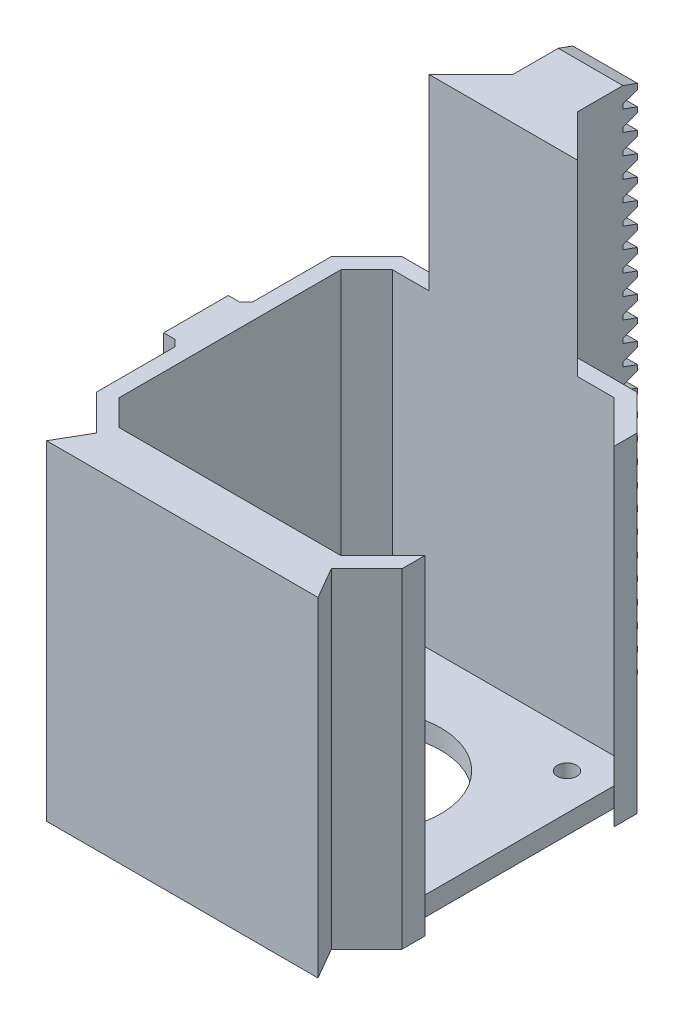
SolidWorks part; units mm, degrees
ref_plane "Front Plane" through (0, 0, 0) normal (0, 0, 1) x (1, 0, 0)
ref_plane "Top Plane" through (0, 0, 0) normal (0, 1, 0) x (1, 0, 0)
ref_plane "Right Plane" through (0, 0, 0) normal (1, 0, 0) x (0, 0, -1)
sketch "Sketch1" plane through (0, 0, 0) normal (0, 1, 0) x (1, 0, 0)
  line L0 (-21.15, 17.15) -> (-17.15, 21.15)
  line L1 (-17.15, -21.15) -> (17.15, -21.15)
  line L2 (-21.15, -17.15) -> (-21.15, 17.15)
  line L3 (-17.15, 21.15) -> (17.15, 21.15)
  line L4 (21.15, -17.15) -> (21.15, 17.15)
  line L5 (-21.15, -21.15) -> (21.15, 21.15) construction
  line L6 (-21.15, 21.15) -> (21.15, -21.15) construction
  line L7 (-21.15, -17.15) -> (-17.15, -21.15)
  line L8 (17.15, -21.15) -> (21.15, -17.15)
  line L9 (17.15, 21.15) -> (21.15, 17.15)
  circle A0 centre (-15.5, 15.5) radius 1.5
  circle A1 centre (15.5, 15.5) radius 1.5
  circle A2 centre (15.5, -15.5) radius 1.5
  circle A3 centre (-15.5, -15.5) radius 1.5
  circle A4 centre (0, 0) radius 11.5
  point P0 (0, 0)
  dimension "D3" = 3
  dimension "D4" = 3
  dimension "D9" = 3
  dimension "D10" = 3
  dimension "D12" = 23
  dimension "D1" = 42.3
  dimension "D2" = 42.3
  dimension "D11" = 31
extrude "Boss-Extrude1" add sketch "Sketch1" along normal blind 3
sketch "Sketch5" plane through (0, 0, 0) normal (0, 1, 0) x (1, 0, 0)
  line L0 (21.15, -17.15) -> (23.65, -14.65)
  line L1 (23.65, -14.65) -> (23.65, 14.65) construction
  line L16 (-23.65, 18.1855) -> (-23.65, -18.1855)
  line L17 (-23.65, -18.1855) -> (-18.1855, -23.65)
  line L18 (-18.1855, -23.65) -> (18.1855, -23.65)
  line L19 (18.1855, -23.65) -> (23.65, -18.1855)
  line L20 (23.65, -18.1855) -> (23.65, 18.1855)
  line L21 (23.65, 18.1855) -> (18.1855, 23.65)
  line L22 (18.1855, 23.65) -> (-18.1855, 23.65)
  line L23 (-18.1855, 23.65) -> (-23.65, 18.1855)
  line L24 (-23.65, 14.65) -> (-23.65, -18.1855)
  line L25 (-23.65, -18.1855) -> (-18.1855, -23.65)
  line L26 (-18.1855, -23.65) -> (18.1855, -23.65)
  line L27 (18.1855, -23.65) -> (23.65, -18.1855)
  line L28 (23.65, -18.1855) -> (23.65, -14.65)
  line L29 (23.65, 18.1855) -> (18.1855, 23.65)
  line L30 (18.1855, 23.65) -> (-18.1855, 23.65)
  line L31 (-18.1855, 23.65) -> (-23.65, 18.1855)
  line L32 (-21.15, 17.15) -> (-23.65, 14.65) construction
  line L33 (21.15, 17.15) -> (23.65, 14.65)
  line L34 (-23.65, 18.1855) -> (-23.65, 14.65)
  line L35 (23.65, 14.65) -> (23.65, 18.1855)
  line L40 (-21.15, 17.15) -> (-21.15, -17.15)
  line L41 (-21.15, -17.15) -> (-17.15, -21.15)
  line L42 (-17.15, -21.15) -> (17.15, -21.15)
  line L43 (17.15, -21.15) -> (21.15, -17.15)
  line L44 (21.15, -17.15) -> (21.15, 17.15)
  line L45 (21.15, 17.15) -> (17.15, 21.15)
  line L46 (17.15, 21.15) -> (-17.15, 21.15)
  line L47 (-17.15, 21.15) -> (-21.15, 17.15)
  line L48 (-21.15, 17.15) -> (-21.15, -17.15)
  line L49 (-21.15, -17.15) -> (-17.15, -21.15)
  line L50 (-17.15, -21.15) -> (17.15, -21.15)
  line L51 (17.15, -21.15) -> (21.15, -17.15)
  line L52 (21.15, -17.15) -> (21.15, 17.15) construction
  line L53 (21.15, 17.15) -> (17.15, 21.15)
  line L54 (17.15, 21.15) -> (-17.15, 21.15)
  line L55 (-17.15, 21.15) -> (-21.15, 17.15)
  dimension "D1" = 2.5
  dimension "D2" = 0
extrude "Boss-Extrude2" add sketch "Sketch5" along normal blind 51
sketch "Sketch9" plane through (0, 0, 0) normal (0, 1, 0) x (1, 0, 0)
  line L0 (-18.1855, -23.65) -> (-21, -28.5248)
  line L1 (-21, -28.5248) -> (21, -28.5248)
  line L2 (21, -28.5248) -> (18.1855, -23.65)
  line L3 (18.1855, -23.65) -> (-18.1855, -23.65)
  dimension "D1" = 60
  dimension "D2" = 60
  dimension "D3" = 42
extrude "Boss-Extrude3" add sketch "Sketch9" along normal blind 51
sketch "Sketch11" plane through (0, 0, 0) normal (1, 0, 0) x (0, 0, -1)
  line L0 (18.1855, 0) -> (23.65, 0) construction
  line L1 (23.65, 51) -> (24.65, 51)
  line L2 (23.65, 51) -> (23.65, 0)
  line L3 (23.65, 0) -> (24.65, 0)
  line L4 (24.65, 51) -> (24.65, 0)
  dimension "D1" = 1
extrude "Boss-Extrude4" add sketch "Sketch11" along normal mid plane 10
sketch "Sketch13" plane through (5, 0, 0) normal (1, 0, 0) x (0, 0, -1)
  line L0 (24.65, 80) -> (34.65, 80)
  line L1 (34.65, 80) -> (36.9, 79.1811)
  line L2 (36.9, 79.1811) -> (36.9, 78.3382)
  line L3 (36.9, 78.3382) -> (34.65, 77.5193)
  line L4 (34.65, 77.5193) -> (34.65, 76.8584)
  line L5 (34.65, 76.8584) -> (36.9, 76.0395)
  line L6 (36.9, 76.0395) -> (36.9, 75.1966)
  line L7 (36.9, 75.1966) -> (34.65, 74.3777)
  line L8 (34.65, 74.3777) -> (34.65, 73.7168)
  line L9 (34.65, 73.7168) -> (36.9, 72.8979)
  line L10 (36.9, 72.8979) -> (36.9, 72.055)
  line L11 (36.9, 72.055) -> (34.65, 71.2361)
  line L12 (34.65, 71.2361) -> (34.65, 70.5752)
  line L13 (34.65, 70.5752) -> (36.9, 69.7563)
  line L14 (36.9, 69.7563) -> (36.9, 68.9134)
  line L15 (36.9, 68.9134) -> (34.65, 68.0945)
  line L16 (34.65, 68.0945) -> (34.65, 67.4336)
  line L17 (34.65, 67.4336) -> (36.9, 66.6147)
  line L18 (36.9, 66.6147) -> (36.9, 65.7718)
  line L19 (36.9, 65.7718) -> (34.65, 64.9529)
  line L20 (34.65, 64.9529) -> (34.65, 64.292)
  line L21 (34.65, 64.292) -> (36.9, 63.4731)
  line L22 (36.9, 63.4731) -> (36.9, 62.6302)
  line L23 (36.9, 62.6302) -> (34.65, 61.8113)
  line L24 (34.65, 61.8113) -> (34.65, 61.1504)
  line L25 (34.65, 61.1504) -> (36.9, 60.3315)
  line L26 (36.9, 60.3315) -> (36.9, 59.4887)
  line L27 (36.9, 59.4887) -> (34.65, 58.6697)
  line L28 (34.65, 58.6697) -> (34.65, 58.0089)
  line L29 (34.65, 58.0089) -> (36.9, 57.1899)
  line L30 (36.9, 57.1899) -> (36.9, 56.3471)
  line L31 (36.9, 56.3471) -> (34.65, 55.5281)
  line L32 (34.65, 55.5281) -> (34.65, 54.8673)
  line L33 (34.65, 54.8673) -> (36.9, 54.0483)
  line L34 (36.9, 54.0483) -> (36.9, 53.2055)
  line L35 (36.9, 53.2055) -> (34.65, 52.3865)
  line L36 (34.65, 52.3865) -> (34.65, 51.7257)
  line L37 (34.65, 51.7257) -> (36.9, 50.9067)
  line L38 (36.9, 50.9067) -> (36.9, 50.0639)
  line L39 (36.9, 50.0639) -> (34.65, 49.2449)
  line L40 (34.65, 49.2449) -> (34.65, 48.5841)
  line L41 (34.65, 48.5841) -> (36.9, 47.7651)
  line L42 (36.9, 47.7651) -> (36.9, 46.9223)
  line L43 (36.9, 46.9223) -> (34.65, 46.1034)
  line L44 (34.65, 46.1034) -> (34.65, 45.4425)
  line L45 (34.65, 45.4425) -> (36.9, 44.6235)
  line L46 (36.9, 44.6235) -> (36.9, 43.7807)
  line L47 (36.9, 43.7807) -> (34.65, 42.9618)
  line L48 (34.65, 42.9618) -> (34.65, 42.3009)
  line L49 (34.65, 42.3009) -> (36.9, 41.482)
  line L50 (36.9, 41.482) -> (36.9, 40.6391)
  line L51 (36.9, 40.6391) -> (34.65, 39.8202)
  line L52 (34.65, 39.8202) -> (34.65, 39.1593)
  line L53 (34.65, 39.1593) -> (36.9, 38.3404)
  line L54 (36.9, 38.3404) -> (36.9, 37.4975)
  line L55 (36.9, 37.4975) -> (34.65, 36.6786)
  line L56 (34.65, 36.6786) -> (34.65, 36.0177)
  line L57 (34.65, 36.0177) -> (36.9, 35.1988)
  line L58 (36.9, 35.1988) -> (36.9, 34.3559)
  line L59 (36.9, 34.3559) -> (34.65, 33.537)
  line L60 (34.65, 33.537) -> (34.65, 32.8761)
  line L61 (34.65, 32.8761) -> (36.9, 32.0572)
  line L62 (36.9, 32.0572) -> (36.9, 31.2143)
  line L63 (36.9, 31.2143) -> (34.65, 30.3954)
  line L64 (34.65, 30.3954) -> (34.65, 29.7345)
  line L65 (34.65, 29.7345) -> (36.9, 28.9156)
  line L66 (36.9, 28.9156) -> (36.9, 28.0727)
  line L67 (36.9, 28.0727) -> (34.65, 27.2538)
  line L68 (34.65, 27.2538) -> (34.65, 26.5929)
  line L69 (34.65, 26.5929) -> (36.9, 25.774)
  line L70 (36.9, 25.774) -> (36.9, 24.9311)
  line L71 (36.9, 24.9311) -> (34.65, 24.1122)
  line L72 (34.65, 24.1122) -> (34.65, 23.4513)
  line L73 (34.65, 23.4513) -> (36.9, 22.6324)
  line L74 (36.9, 22.6324) -> (36.9, 21.7895)
  line L75 (36.9, 21.7895) -> (34.65, 20.9706)
  line L76 (34.65, 20.9706) -> (34.65, 20.3097)
  line L77 (34.65, 20.3097) -> (36.9, 19.4908)
  line L78 (36.9, 19.4908) -> (36.9, 18.648)
  line L79 (36.9, 18.648) -> (34.65, 17.829)
  line L80 (34.65, 17.829) -> (34.65, 17.1681)
  line L81 (34.65, 17.1681) -> (36.9, 16.3492)
  line L82 (36.9, 16.3492) -> (36.9, 15.5064)
  line L83 (36.9, 15.5064) -> (34.65, 14.6874)
  line L84 (34.65, 14.6874) -> (34.65, 14.0266)
  line L85 (34.65, 14.0266) -> (36.9, 13.2076)
  line L86 (36.9, 13.2076) -> (36.9, 12.3648)
  line L87 (36.9, 12.3648) -> (34.65, 11.5458)
  line L88 (34.65, 11.5458) -> (34.65, 10.885)
  line L89 (34.65, 10.885) -> (36.9, 10.066)
  line L90 (36.9, 10.066) -> (36.9, 9.2232)
  line L91 (36.9, 9.2232) -> (34.65, 8.4042)
  line L92 (34.65, 8.4042) -> (34.65, 7.7434)
  line L93 (34.65, 7.7434) -> (36.9, 6.9244)
  line L94 (36.9, 6.9244) -> (36.9, 6.0816)
  line L95 (36.9, 6.0816) -> (34.65, 5.2626)
  line L96 (34.65, 5.2626) -> (34.65, 4.6018)
  line L97 (34.65, 4.6018) -> (36.9, 3.7828)
  line L98 (36.9, 3.7828) -> (36.9, 2.94)
  line L99 (36.9, 2.94) -> (34.65, 2.1211)
  line L100 (34.65, 2.1211) -> (34.65, 1.4602)
  line L101 (34.65, 1.4602) -> (36.9, 0.6413)
  line L102 (36.9, 0.6413) -> (36.9, 0)
  line L103 (36.9, 0) -> (24.65, 0)
  line L104 (24.65, 0) -> (24.65, 80)
  line L105 (24.65, 0) -> (24.65, 51) construction
  line L106 (23.65, 0) -> (24.65, 0) construction
extrude "Boss-Extrude6" add sketch "Sketch13" against normal up to surface (10 mm away) up to face at (-5, 25.5, -24.15)
sketch "Sketch14" plane through (0, 0, 0) normal (1, 0, 0) x (0, 0, -1)
  line L0 (35.65, 0) -> (35.65, 80)
  line L1 (23.65, 0) -> (36.9, 0) construction
  line L2 (34.65, 80) -> (24.65, 80) construction
  line L3 (34.65, 67.4336) -> (34.65, 68.0945) construction
  dimension "D1" = 1
chamfer "Chamfer1" distance 4 angle 45 2 edges at (-5, 25.5, -23.65) (5, 25.5, -23.65)
sketch "Sketch15" plane through (0, 51, 0) normal (0, 1, 0) x (1, 0, 0)
  line L0 (-8, 24.65) -> (-11.5, 21.15)
  line L1 (17.15, 21.15) -> (-17.15, 21.15) construction
  line L2 (-11.5, 21.15) -> (11.5, 21.15)
  line L3 (11.5, 21.15) -> (8, 24.65)
  line L4 (8, 24.65) -> (-8, 24.65)
  line L5 (-5, 27.65) -> (-8, 24.65) construction
  line L6 (8, 24.65) -> (5, 27.65) construction
extrude "Boss-Extrude7" add sketch "Sketch15" along normal up to surface (29 mm away) up to face at (0, 80, -28.9833)
sketch "Sketch16" plane through (0, 51, 0) normal (0, 1, 0) x (1, 0, 0)
  line L0 (-23.65, 18.1855) -> (-23.65, -18.1855) construction
  line L1 (-23.65, -5) -> (-26.4, -5)
  line L2 (-23.65, -5) -> (-23.65, 5)
  line L3 (-23.65, 5) -> (-26.4, 5)
  line L4 (-26.4, -5) -> (-26.4, 5)
  point P6 (-26.4, 0)
  dimension "D1" = 2.75
  dimension "D2" = 10
extrude "Boss-Extrude8" add sketch "Sketch16" against normal offset from surface (4 mm away) 47 up to face at (4.48, 0, -5.9675)
chamfer "Chamfer2" distance 1 angle 45 1 edges at (-23.65, 47, 0)
chamfer "Chamfer3" distance 1 angle 45 2 edges at (-23.65, 48.5, -5) (-23.65, 48.5, 5)
